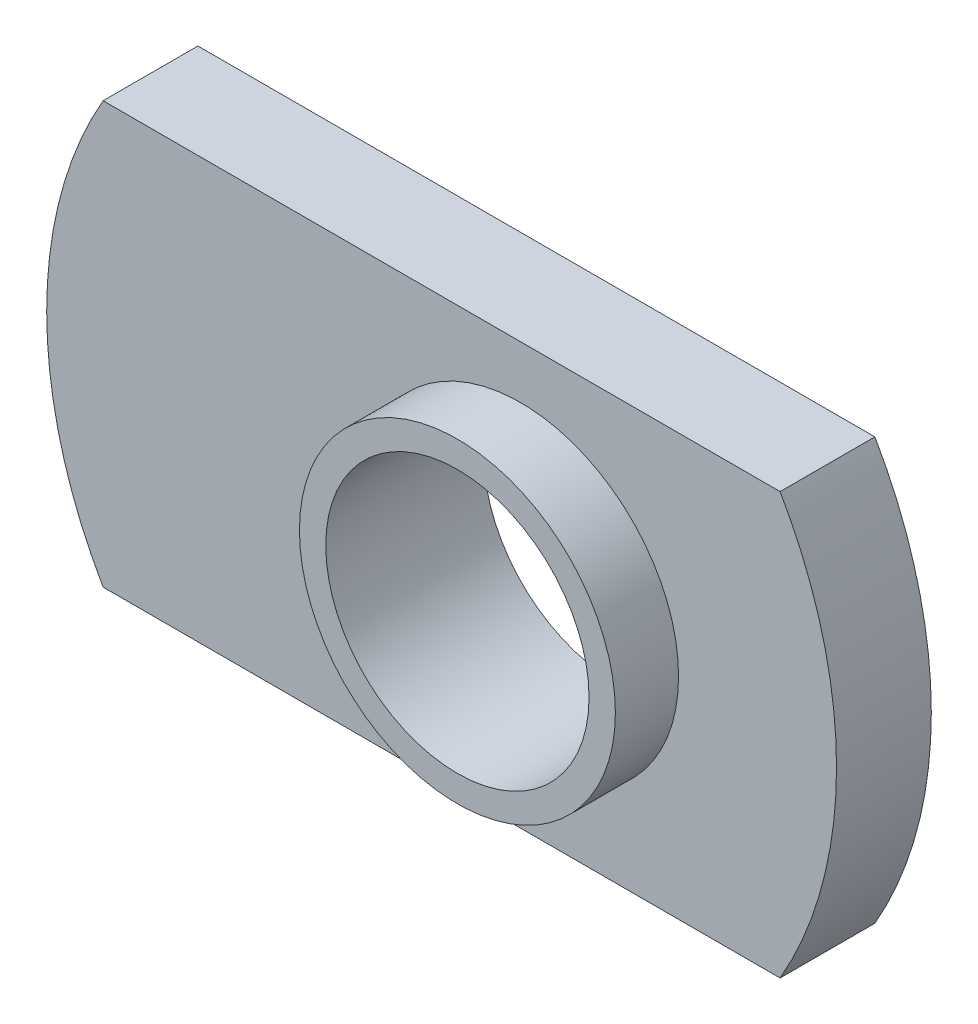
SolidWorks part; units mm, degrees
ref_plane "Front Plane" through (0, 0, 0) normal (0, 0, 1) x (1, 0, 0)
ref_plane "Top Plane" through (0, 0, 0) normal (0, 1, 0) x (1, 0, 0)
ref_plane "Right Plane" through (0, 0, 0) normal (1, 0, 0) x (0, 0, -1)
sketch "Sketch7" plane through (0, 0, 0) normal (0, 0, 1) x (1, 0, 0)
  line L0 (-7.9282, 4) -> (4.9282, 4)
  line L1 (-9, 0) -> (6, 0) construction
  line L2 (0, 0) -> (1.7678, -1.7678) construction
  line L3 (-7.9282, -4) -> (4.9282, -4)
  circle A0 centre (0, 0) radius 2.5 construction
  arc A1 (4.9282, -4) -> (4.9282, 4) centre (-2, 0) ccw
  arc A5 (-7.9282, -4) -> (-7.9282, 4) centre (-1, 0) cw
  circle A6 centre (0, 0) radius 3 construction
  point P8 (1.7678, -1.7678)
  dimension "D1" = 45
  dimension "Thread Dia" = 5
  dimension "Nut Width" = 6
  dimension "Side Radius" = 8
  dimension "Length" = 15
  dimension "Offset" = 6
  dimension "Width" = 8
extrude "Boss-Extrude1" add sketch "Sketch7" along normal mid plane 1.8 separate body
sketch "Sketch8" plane through (0, 0, 0.9) normal (0, 0, 1) x (1, 0, 0)
  circle A2 centre (0, 0) radius 2.5 construction
  circle A3 centre (0, 0) radius 2.5
  circle A4 centre (0, 0) radius 3 construction
  circle A5 centre (0, 0) radius 3
extrude "Boss-Extrude2" add sketch "Sketch8" along normal blind 1.2
sketch "Sketch1" plane through (0, 0, 0) normal (0, 0, 1) x (1, 0, 0)
  circle A0 centre (0, 0) radius 2.5
  circle A3 centre (0, 0) radius 2.5 construction
extrude "Cut-Extrude1" cut sketch "Sketch1" against normal through all both and the other way through all
sketch "Sketch6" plane through (0, 0, -0.9) normal (0, 0, -1) x (-1, 0, 0)
  line L0 (-6, 4) -> (-6, -4) construction
  line L1 (-6, 4) -> (9, 4) construction
  line L2 (-6, -4) -> (9, -4) construction
  line L3 (9, 4) -> (9, -4) construction
  line L6 (7.9282, -4) -> (-4.9282, -4) construction
  line L7 (7.9282, 4) -> (-4.9282, 4) construction
  arc A2 (7.9282, -4) -> (7.9282, 4) centre (1, 0) ccw construction
  arc A3 (-4.9282, 4) -> (-4.9282, -4) centre (2, 0) ccw construction
sketch "Sketch2" [suppressed] plane through (0, 0, -0.9) normal (0, 0, -1) x (-1, 0, 0)
  circle A2 centre (0, 0) radius 2.5
  circle A3 centre (0, 0) radius 2.5
  dimension "D1" = 0
sketch "Sketch3" [suppressed] plane through (0, 0, 0) normal (1, 0, 0) x (0, 0, -1)
  line L0 (0.85, 2.5866) -> (1.65, 2.5866) construction
  line L1 (1.65, 2.5866) -> (1.25, 1.8938) construction
  line L2 (1.25, 1.8938) -> (0.85, 2.5866) construction
  line L3 (0.875, 2.5433) -> (1.625, 2.5433) construction
  line L5 (0.9, 2.5) -> (1.6, 2.5) construction
  line L7 (1.2, 1.9804) -> (1.3, 1.9804) construction
  line L8 (0.875, 2.5433) -> (1.625, 2.5433)
  line L9 (1.625, 2.5433) -> (1.3, 1.9804)
  line L10 (1.25, 1.9804) -> (1.25, 1.8938) construction
  line L11 (1.25, 2.5866) -> (1.25, 2.5) construction
  line L12 (1.3, 1.9804) -> (1.2, 1.9804)
  line L13 (1.2, 1.9804) -> (0.875, 2.5433)
  point P9 (1.25, 2.5433)
  dimension "D2" = 0.1
curve "Helix/Spiral1" [suppressed] pitch 0.8 height 3.8 turns 4.75
sweep "Sweep1" [suppressed] add profiles "Sketch3" path "Helix/Spiral1"
split "Split1" [suppressed] bodies to split 106
sketch "Sketch4" [suppressed] plane through (0, 0, -0.9) normal (0, 0, -1) x (-1, 0, 0)
  circle A1 centre (0, 0) radius 2.5
  circle A2 centre (0, 0) radius 2.5
  dimension "D1" = 0
extrude "Cut-Extrude2" [suppressed] cut sketch "Sketch4" against normal through all draft 45
sketch "Sketch5" [suppressed] plane through (0, 0, 2.1) normal (0, 0, 1) x (1, 0, 0)
  circle A1 centre (0, 0) radius 2.5
  circle A2 centre (0, 0) radius 2.5
  dimension "D1" = 0
extrude "Cut-Extrude3" [suppressed] cut sketch "Sketch5" against normal through all draft 45
ref_plane "Contact Plane 1" through (0, 0, -0.9) normal (0, 0, -1) x (-1, 0, 0)
ref_axis "Center Axis 1" through (0, 0, 2.5981) along (0, 0, -1)
equation "\"D2@Sketch3\" = \"Pitch@Sketch3\" / 8"
equation "\"D4@Helix/Spiral1\"=\"Pitch@Sketch3\""
equation "\"D3@Helix/Spiral1\" = \"Nut Thickness@Boss-Extrude1\" + \"Thread Depth@Boss-Extrude2\" + \"Pitch@Sketch3\""
